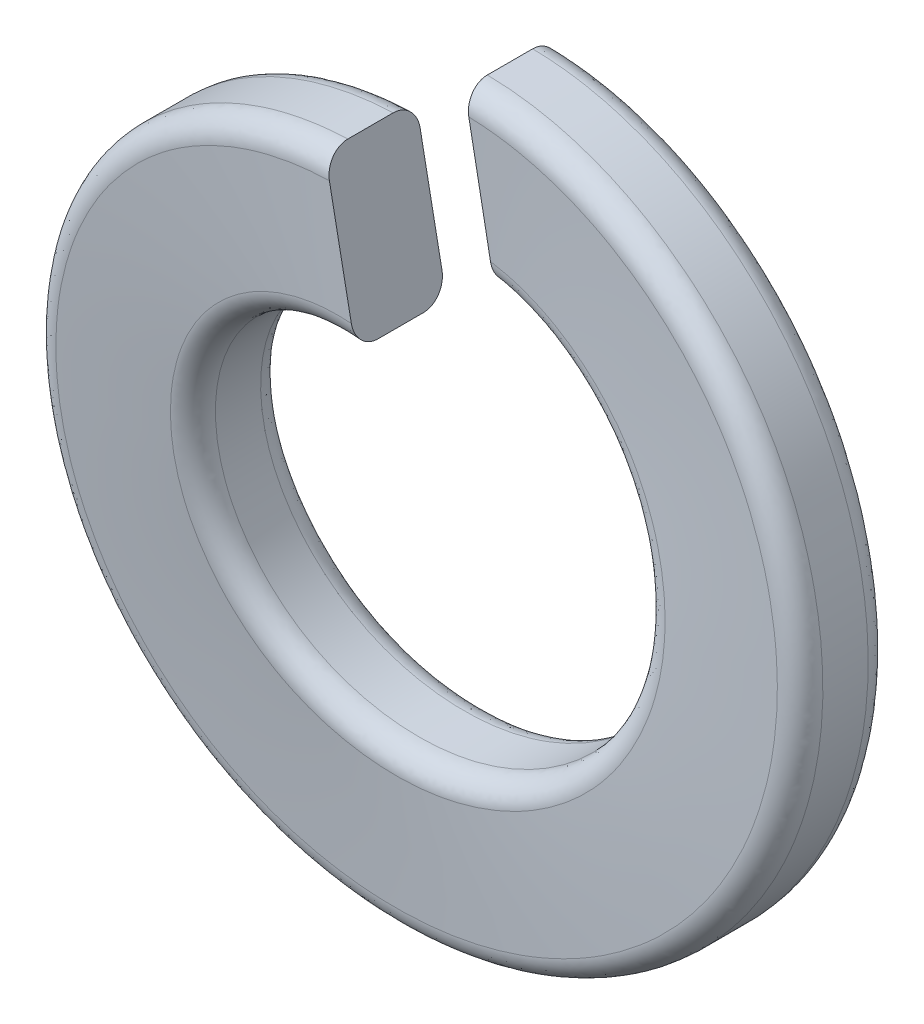
SolidWorks part; units mm, degrees
ref_plane "Front Plane" through (0, 0, 0) normal (0, 0, 1) x (1, 0, 0)
ref_plane "Top Plane" through (0, 0, 0) normal (0, 1, 0) x (1, 0, 0)
ref_plane "Right Plane" through (0, 0, 0) normal (1, 0, 0) x (0, 0, -1)
sketch "Sketch1" plane through (0, 0, 0) normal (0, 0, 1) x (1, 0, 0)
  line L0 (0, -3.1) -> (0, 3.1) construction
  line L1 (-0.1352, 3.097) -> (0.1378, 1.6944) construction
  line L2 (0, 0) -> (-0.85, -1.4722) construction
  line L3 (0, 1.7) -> (-0.2702, 3.0882) construction
  line L4 (0, 0) -> (-0.2702, 3.0882) construction
  line L5 (-0.1352, 3.097) -> (0, 0) construction
  circle A0 centre (0, 0) radius 3.1 construction
  circle A1 centre (0, 0) radius 1.7 construction
  point P6 (0, -1.7)
  dimension "ID" = 3.4
  dimension "OD" = 6.2
  dimension "D2" = 5
  dimension "D1" = 30
  dimension "D3" = 2.5
sketch "Sketch2" plane through (0, 0, 0) normal (1, 0, 0) x (0, 0, -1)
  line L0 (-0.95, 0) -> (0.95, 0) construction
  line L1 (0, -3.1) -> (0, 3.1) construction
  line L2 (-0.95, 3.1) -> (-0.15, 3.1) construction
  line L3 (-0.95, 3.1) -> (-0.95, 1.7) construction
  line L4 (-0.95, 1.7) -> (-0.15, 1.7) construction
  line L5 (-0.15, 3.1) -> (-0.15, 1.7) construction
  line L6 (0, -3.1) -> (0, 3.1) construction
  line L12 (-0.4, -1.7) -> (0.4, -1.7) construction
  line L13 (-0.4, -1.7) -> (-0.4, -3.1) construction
  line L14 (-0.4, -3.1) -> (0.4, -3.1) construction
  line L15 (0.4, -1.7) -> (0.4, -3.1) construction
  point P8 (-0.55, 3.1)
  point P13 (0.4, -2.9)
  point P15 (0.95, 3.1)
  point P19 (0.55, 3.1)
  dimension "Thickness" = 0.8
  dimension "Helix Height" = 1.1
  dimension "Height" = 1.9
  dimension "Radius" = 0.2
ref_plane "Plane1" through (0, 0, 0.55) normal (0, 0, 1) x (1, 0, 0)
sketch "Sketch3" plane through (0, 0, 0.55) normal (0, 0, 1) x (1, 0, 0)
  circle A0 centre (0, 0) radius 3.1 construction
  circle A1 centre (0, 0) radius 3.1
curve "Helix/Spiral1" pitch 1.1011 height 1.1 turns 0.999
ref_plane "Plane2" through (0.3188, 0.062, 0) normal (0.9816, 0.191, 0) x (0.0067, -0.0343, -0.9994)
sketch "Sketch4" plane through (0.3464, -0.08, 0.0051) normal (0.9816, 0.191, 0) x (0.0067, -0.0343, -0.9994)
  line L0 (-1.0558, 3.1526) -> (-0.2563, 3.1806) construction
  line L10 (-1.0078, 1.7793) -> (-0.2083, 1.8072) construction
  line L12 (-1.0572, 3.1926) -> (-0.2577, 3.2206)
  line L13 (-0.2577, 3.2206) -> (-0.2083, 1.8072)
  line L14 (-1.0078, 1.7793) -> (-0.2083, 1.8072)
  line L15 (-1.0572, 3.1926) -> (-1.0078, 1.7793)
sweep "Sweep1" add profiles "Sketch4" path "Helix/Spiral1"
sketch "Sketch5" plane through (0, 0, 0) normal (0, 0, 1) x (1, 0, 0)
  line L0 (0, 1.7) -> (-0.2702, 3.0882) construction
  line L1 (-0.1352, 3.097) -> (0.1378, 1.6944) construction
  line L2 (0, 1.7) -> (-0.2702, 3.0882)
  line L3 (-0.1352, 3.097) -> (0.1378, 1.6944)
  circle A0 centre (0, 0) radius 1.7 construction
  circle A1 centre (0, 0) radius 3.1 construction
  arc A2 (0.1378, 1.6944) -> (0, 1.7) centre (0, 0) ccw
  arc A3 (-0.1352, 3.097) -> (-0.2702, 3.0882) centre (0, 0) ccw
extrude "Cut-Extrude1" cut sketch "Sketch5" against normal through all
fillet "Fillet1" radius 0.2 4 edges
equation "\"D3@Helix/Spiral1\"=\"Helix Height@Sketch2\""
equation "\"D7@Helix/Spiral1\"=90+\"D2@Sketch1\""
equation "\"D1@Fillet1\"=\"Radius@Sketch2\""
equation "\"D3@Sketch1\"=\"D2@Sketch1\"/2"
